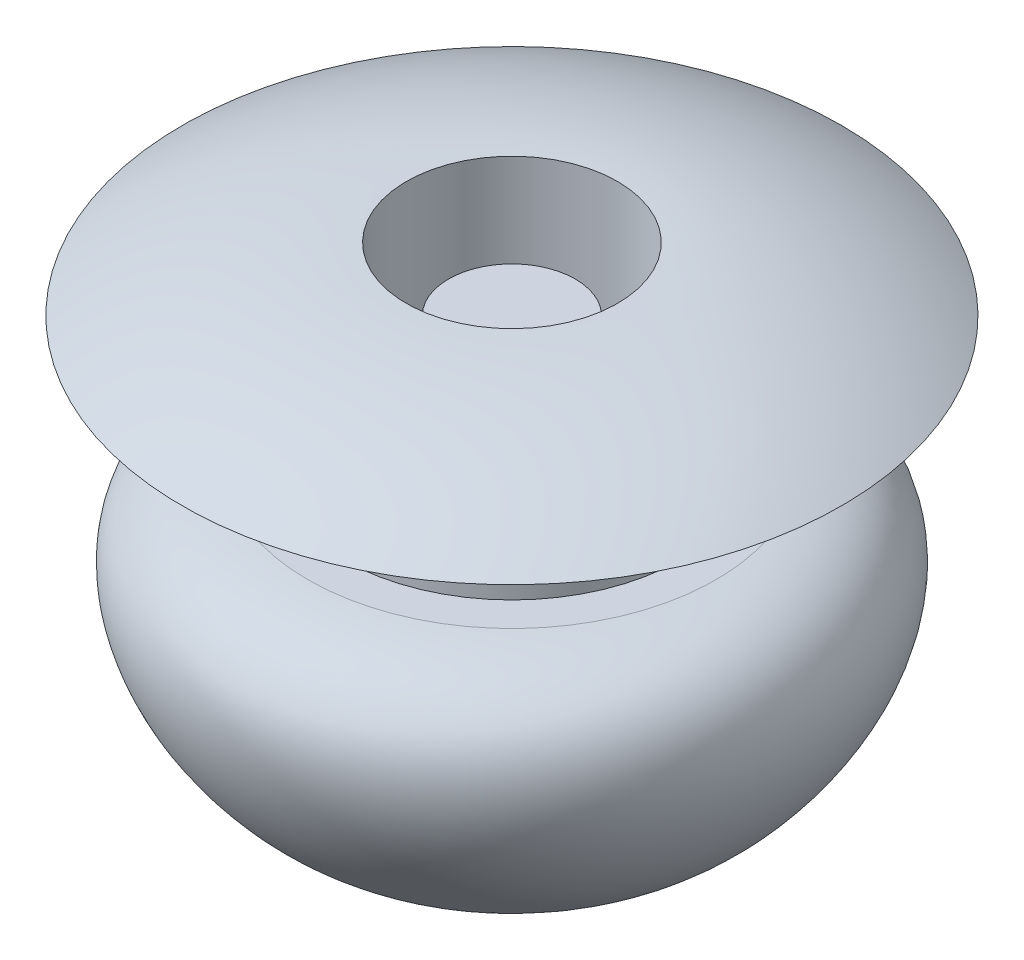
SolidWorks part; units mm, degrees
material "AISI 316 Stal nierdzewna odprężona (SS)"
ref_plane "Płaszczyzna przednia" through (0, 0, 0) normal (0, 0, 1) x (1, 0, 0)
ref_plane "Płaszczyzna górna" through (0, 0, 0) normal (0, 1, 0) x (1, 0, 0)
ref_plane "Płaszczyzna prawa" through (0, 0, 0) normal (1, 0, 0) x (0, 0, -1)
sketch "Szkic1" plane through (0, 0, 0) normal (1, 0, 0) x (0, 0, -1)
  line L1 (0, 0) -> (-0.75, 0)
  line L2 (-0.75, 0) -> (-0.75, -1.7007)
  line L3 (-0.75, -1.7007) -> (-1.25, -1.7007)
  line L4 (-1.25, -1.7007) -> (-1.25, 0.75)
  line L5 (-3.9, 0) -> (-2, 0)
  line L6 (-2, 0) -> (-2, -1.5)
  line L7 (-2, -1.5) -> (-2.4139, -1.5)
  line L8 (0, 0) -> (0, 0.4842) construction
  line L9 (0, -1.7007) -> (0, 0)
  line L10 (0, -1.7007) -> (0, -3.2007)
  line L11 (-10.4007, -1.5) -> (-6.4007, -1.5) construction
  arc A0 (-1.25, 0.75) -> (-3.9, 0) centre (-1.25, -4.3067) ccw
  ellipse E0 centre (0, -2.4507) end of major axis (-1.75, -2.4507) minor radius 0.75 (-0.956, -3.0789) -> (0, -3.2007) ccw
  spline S0 degree 3 poles (-2.4139, -1.5) (-3.8675, -1.6697) (-3.5289, -3.802) (-1.084, -5.3735) (-0.2718, -3.375) (-0.956, -3.0789) knots 0 0 0 0 0.464993 0.721928 1 1 1 1
  dimension "D1" = 7.8
  dimension "D2" = 2.5
  dimension "D3" = 4
  dimension "D4" = 0.75
  dimension "D5" = 1.5
  dimension "D6" = 1.5
  dimension "D7" = 3.5
  dimension "D8" = 3.1855
  dimension "D9" = 2.5026
  dimension "D10" = 1.9
  dimension "D11" = 1.5789
  dimension "D12" = 0.5792
  dimension "D13" = 4.8278
  dimension "D14" = 3.3858
  dimension "D15" = 2.8395
  dimension "D16" = 1.25
  dimension "D17" = 0.6409
  dimension "D18" = 0.956
revolve "Obrót1" add sketch "Szkic1" angle 360 about L8
